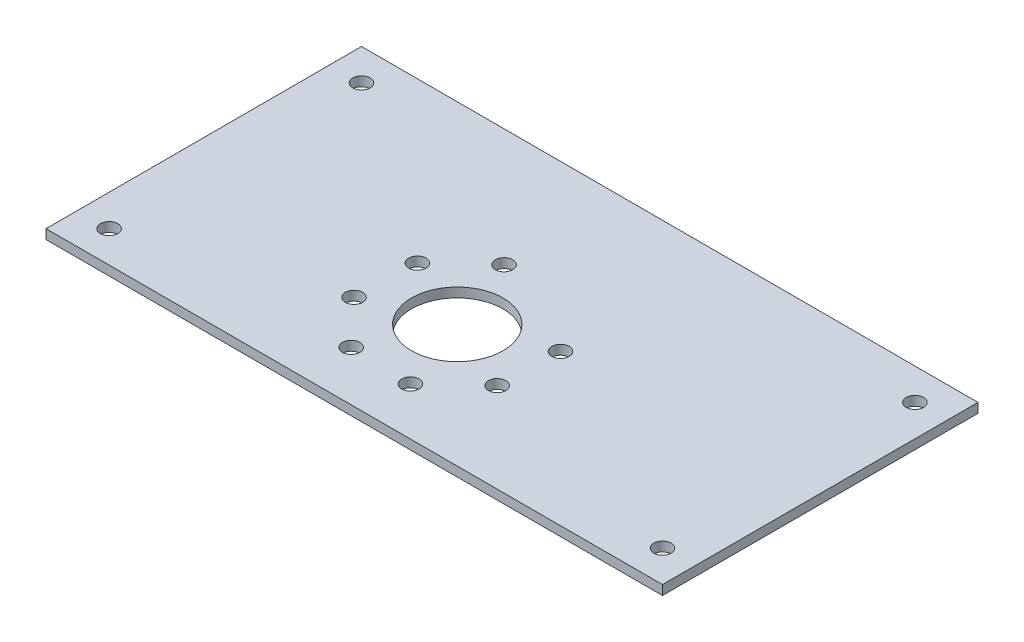
SolidWorks part; units mm, degrees
ref_plane "Front Plane" through (0, 0, 0) normal (0, 0, 1) x (1, 0, 0)
ref_plane "Top Plane" through (0, 0, 0) normal (0, 1, 0) x (1, 0, 0)
ref_plane "Right Plane" through (0, 0, 0) normal (1, 0, 0) x (0, 0, -1)
sketch "Sketch1" plane through (0, 0, 0) normal (0, 1, 0) x (1, 0, 0)
  line L1 (0, 0) -> (195.38, 0)
  line L2 (0, 0) -> (0, -100)
  line L3 (0, -100) -> (195.38, -100)
  line L4 (195.38, 0) -> (195.38, -100)
  dimension "D1" = 195.38
  dimension "D2" = 100
extrude "Boss-Extrude1" add sketch "Sketch1" along normal blind 3
sketch "Sketch2" plane through (0, 3, 0) normal (0, 1, 0) x (1, 0, 0)
  line L0 (195.38, 0) -> (0, 0) construction
  line L1 (195.38, -100) -> (195.38, 0) construction
  line L2 (0, -100) -> (195.38, -100) construction
  circle A2 centre (185.38, -10) radius 2.75
  circle A3 centre (185.38, -90) radius 2.75
  circle A4 centre (9.988, -90) radius 2.75
  circle A5 centre (9.988, -10) radius 2.75
  dimension "D1" = 5.5
  dimension "D2" = 10
  dimension "D3" = 5.5
  dimension "D4" = 5.5
  dimension "D5" = 5.5
  dimension "D6" = 10
  dimension "D7" = 10
extrude "Cut-Extrude1" cut sketch "Sketch2" against normal through all
sketch "Sketch3" plane through (0, 3, 0) normal (0, 1, 0) x (1, 0, 0)
  circle A21 centre (80.9459, -84.2274) radius 2.0193 construction
  circle A22 centre (67.6605, -70.035) radius 2.0193 construction
  circle A23 centre (100.3756, -84.8688) radius 2.0193 construction
  circle A24 centre (114.5681, -71.5835) radius 2.0193 construction
  circle A25 centre (115.2095, -52.1537) radius 2.0193 construction
  circle A26 centre (82.4944, -37.3199) radius 2.0193 construction
  circle A27 centre (68.3019, -50.6052) radius 2.0193 construction
  circle A28 centre (80.9459, -84.2274) radius 2.0193 construction
  circle A29 centre (67.6605, -70.035) radius 2.0193 construction
  circle A30 centre (100.3756, -84.8688) radius 2.0193 construction
  circle A31 centre (114.5681, -71.5835) radius 2.0193 construction
  circle A32 centre (115.2095, -52.1537) radius 2.0193 construction
  circle A33 centre (82.4944, -37.3199) radius 2.0193 construction
  circle A34 centre (68.3019, -50.6052) radius 2.0193 construction
  circle A35 centre (82.4944, -37.3199) radius 2.75
  circle A36 centre (68.3019, -50.6052) radius 2.75
  circle A37 centre (67.6605, -70.035) radius 2.75
  circle A38 centre (115.2095, -52.1537) radius 2.75
  circle A39 centre (114.5681, -71.5835) radius 2.75
  circle A40 centre (100.3756, -84.8688) radius 2.75
  circle A41 centre (80.9459, -84.2274) radius 2.75
  circle A42 centre (91.435, -61.0943) radius 9.525 construction
  circle A43 centre (91.435, -61.0943) radius 9.525 construction
  circle A44 centre (91.435, -61.0943) radius 14.5
  dimension "D1" = 5.5
  dimension "D2" = 5.5
  dimension "D3" = 5.5
  dimension "D4" = 5.5
  dimension "D5" = 5.5
  dimension "D6" = 5.5
  dimension "D7" = 5.5
  dimension "D8" = 29
extrude "Cut-Extrude2" cut sketch "Sketch3" against normal through all
